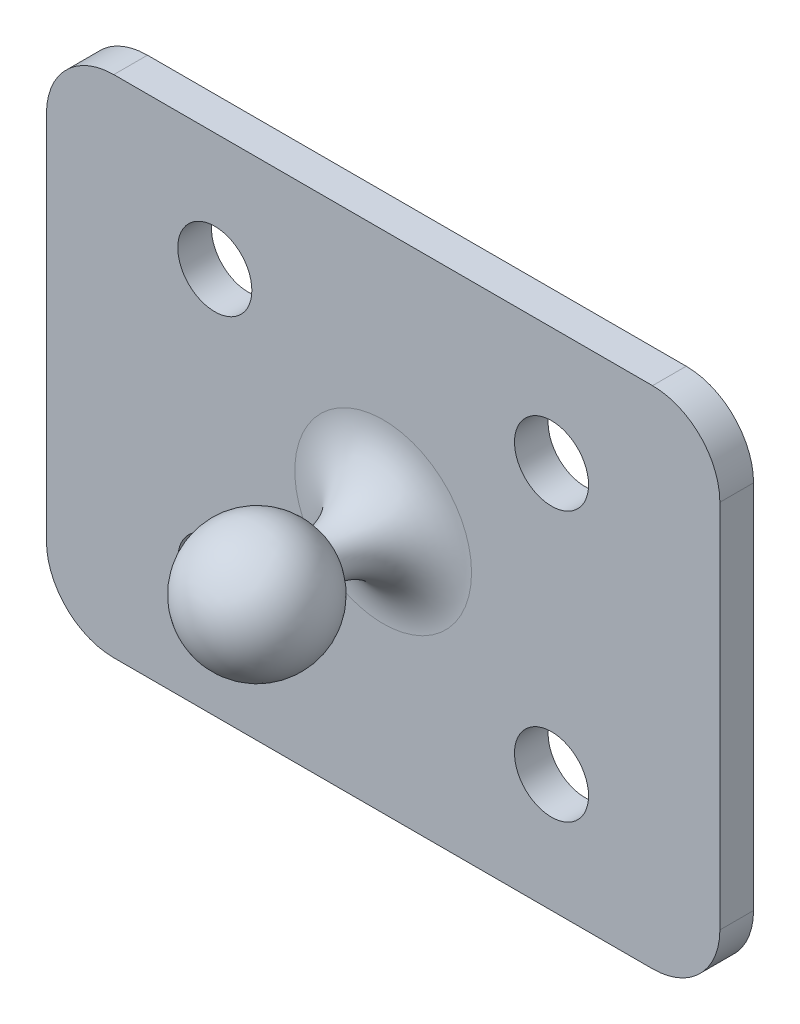
SolidWorks part; units mm, degrees
ref_plane "Front Plane" through (0, 0, 0) normal (0, 0, 1) x (1, 0, 0)
ref_plane "Top Plane" through (0, 0, 0) normal (0, 1, 0) x (1, 0, 0)
ref_plane "Right Plane" through (0, 0, 0) normal (1, 0, 0) x (0, 0, -1)
sketch "Sketch1" plane through (0, 0, 0) normal (0, 0, 1) x (1, 0, 0)
  line L1 (16.51, -12.7) -> (57.15, -12.7)
  line L2 (11.43, -17.78) -> (11.43, -45.72)
  line L3 (16.51, -50.8) -> (57.15, -50.8)
  line L4 (62.23, -17.78) -> (62.23, -45.72)
  arc A0 (11.43, -45.72) -> (16.51, -50.8) centre (16.51, -45.72) ccw
  arc A1 (57.15, -50.8) -> (62.23, -45.72) centre (57.15, -45.72) ccw
  arc A2 (57.15, -12.7) -> (62.23, -17.78) centre (57.15, -17.78) cw
  arc A3 (16.51, -12.7) -> (11.43, -17.78) centre (16.51, -17.78) ccw
  dimension "D5" = 5.08
  dimension "D1" = 38.1
  dimension "D2" = 50.8
extrude "Boss-Extrude1" add sketch "Sketch1" along normal blind 2.54
sketch "Sketch2" plane through (0, 0, 2.54) normal (0, 0, 1) x (1, 0, 0)
  line L0 (57.15, -12.7) -> (16.51, -12.7) construction
  line L1 (11.43, -17.78) -> (11.43, -45.72) construction
  circle A0 centre (24.13, -21.59) radius 2.794
  circle A1 centre (49.53, -21.59) radius 2.794
  circle A2 centre (24.13, -41.91) radius 2.794
  circle A3 centre (49.53, -41.91) radius 2.794
  dimension "D1" = 5.588
  dimension "D2" = 5.588
  dimension "D3" = 5.588
  dimension "D4" = 5.588
  dimension "D5" = 25.4
  dimension "D6" = 20.32
  dimension "D7" = 20.32
  dimension "D8" = 25.4
  dimension "D9" = 8.89
  dimension "D11" = 12.7
extrude "Cut-Extrude1" cut sketch "Sketch2" against normal through all
sketch "Sketch3" plane through (0, 0, 2.54) normal (0, 0, 1) x (1, 0, 0)
  line L0 (36.83, -12.7) -> (36.83, -50.8) construction
  line L1 (57.15, -12.7) -> (16.51, -12.7) construction
  line L2 (16.51, -50.8) -> (57.15, -50.8) construction
  line L3 (11.43, -31.75) -> (62.23, -31.75) construction
  line L4 (11.43, -17.78) -> (11.43, -45.72) construction
  line L5 (62.23, -45.72) -> (62.23, -17.78) construction
  circle A0 centre (36.83, -31.75) radius 1.5875
  dimension "D1" = 3.175
extrude "Boss-Extrude2" add sketch "Sketch3" along normal blind 9.525
fillet "Fillet1" radius 5.08 1 edges at (38.4175, -31.75, 2.54)
sketch "Sketch5" plane through (0, 0, 12.065) normal (0, 0, 1) x (1, 0, 0)
  line L0 (36.83, -30.1625) -> (36.83, -33.3375) construction
  line L1 (36.83, -26.9875) -> (36.83, -36.5125)
  circle A0 centre (36.83, -31.75) radius 1.5875 construction
  arc A1 (36.83, -26.9875) -> (36.83, -36.5125) centre (36.83, -31.75) ccw
  dimension "D1" = 9.525
revolve "Revolve1" add sketch "Sketch5" angle 360 about L0
